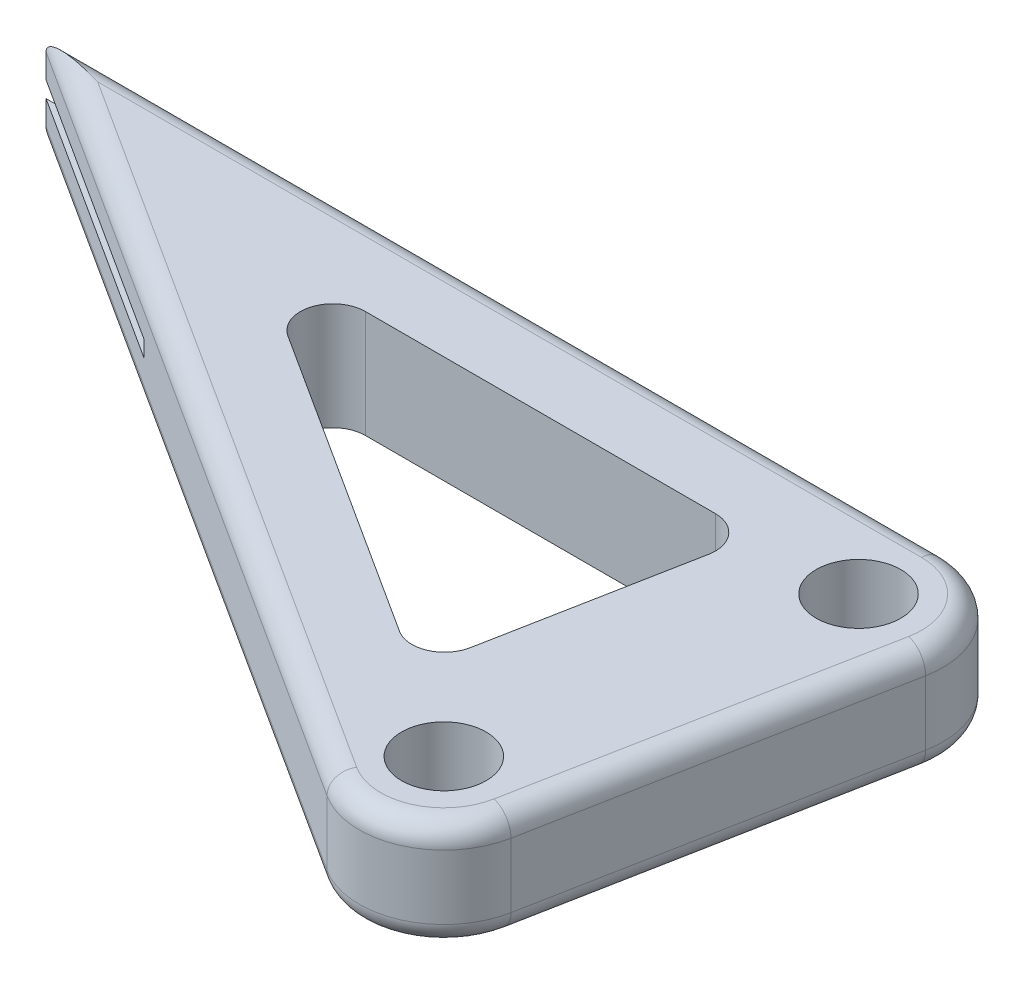
SolidWorks part; units mm, degrees
ref_plane "Front Plane" through (0, 0, 0) normal (0, 0, 1) x (1, 0, 0)
ref_plane "Top Plane" through (0, 0, 0) normal (0, 1, 0) x (1, 0, 0)
ref_plane "Right Plane" through (0, 0, 0) normal (1, 0, 0) x (0, 0, -1)
sketch "Sketch1" plane through (0, 0, 0) normal (0, 1, 0) x (1, 0, 0)
  line L0 (-77.4108, -8.4155) -> (-13.2849, -49.5774)
  line L1 (1.9384, -43.0429) -> (9.8215, -1.881)
  line L2 (-72.009, 10) -> (0, 10)
  line L3 (-7.8831, -41.1619) -> (0, 0) construction
  line L4 (0, 0) -> (-72.009, 0) construction
  line L5 (-72.009, 0) -> (-7.8831, -41.1619) construction
  line L6 (-72.009, 10) -> (-106.1002, 10)
  line L7 (-106.1002, 10) -> (-77.4108, -8.4155)
  arc A0 (-77.4108, -8.4155) -> (-72.009, 10) centre (-72.009, 0) cw construction
  arc A1 (9.8215, -1.881) -> (0, 10) centre (0, 0) ccw
  arc A2 (-13.2849, -49.5774) -> (1.9384, -43.0429) centre (-7.8831, -41.1619) ccw
  circle A4 centre (0, 0) radius 5
  circle A5 centre (-7.8831, -41.1619) radius 5
  dimension "D4" = 10
  dimension "D5" = 10
  dimension "D1" = 76.2
  dimension "D2" = 72.009
  dimension "D3" = 41.91
extrude "Boss-Extrude1" add sketch "Sketch1" along normal blind 12.7
fillet "Fillet1" radius 2.54 10 edges at (-53.0501, 0, -10) (7.7074, 0, -6.3714) (5.88, 0, 22.4619) (-3.9387, 0, 50.3512) (-53.0501, 12.7, -10) (7.7074, 12.7, -6.3714) (5.88, 12.7, 22.4619) (-3.9387, 12.7, 50.3512) (-59.6925, 0, 19.7887) (-59.6925, 12.7, 19.7887)
scale "Scale1" scale about centroid uniform scaling yes scale factor 0.66
sketch "Sketch2" plane through (0, 10.541, 0) normal (0, 1, 0) x (1, 0, 0)
  line L0 (-58.3493, -4.1878) -> (-23.5786, -26.5068)
  line L1 (-23.5786, -26.5068) -> (-19.3042, -4.1878)
  line L2 (-19.3042, -4.1878) -> (-58.3493, -4.1878)
  line L3 (-11.3565, 0.8922) -> (-75.6676, 0.8922) construction
  line L4 (-75.6676, 0.8922) -> (-19.219, -35.3417) construction
  line L5 (-11.7237, -32.1243) -> (-6.5208, -4.9575) construction
  dimension "D1" = 5.08
  dimension "D2" = 5.08
  dimension "D3" = 12.7
extrude "Cut-Extrude1" cut sketch "Sketch2" against normal through all
fillet "Fillet2" radius 2.54 3 edges at (-23.5786, 6.35, 26.5068) (-19.3042, 6.35, 4.1878) (-58.3493, 6.35, 4.1878)
ref_plane "Plane1" through (-58.8031, 0, -37.7452) normal (-0.8415, 0, -0.5402) x (0, -1, 0)
sketch "Sketch3" plane through (-58.8031, 0, -37.7452) normal (-0.8415, 0, -0.5402) x (0, -1, 0)
  line L0 (-5.715, 41.7999) -> (-5.715, 39.8949)
  line L1 (-8.8646, 41.7999) -> (-3.8354, 41.7999) construction
  line L2 (-5.715, 39.8949) -> (-5.08, 39.8949)
  line L3 (-5.08, 39.8949) -> (-5.08, 38.6249)
  line L4 (-5.08, 38.6249) -> (-7.62, 38.6249)
  line L5 (-7.62, 38.6249) -> (-7.62, 39.8949)
  line L6 (-7.62, 39.8949) -> (-6.985, 39.8949)
  line L7 (-6.985, 39.8949) -> (-6.985, 41.7999)
  line L8 (-6.985, 41.7999) -> (-5.715, 41.7999)
  point P15 (-6.35, 41.7999)
  dimension "D1" = 1.905
  dimension "D2" = 2.54
  dimension "D3" = 1.27
  dimension "D4" = 1.27
extrude "Cut-Extrude2" cut sketch "Sketch3" against normal blind 25.4
